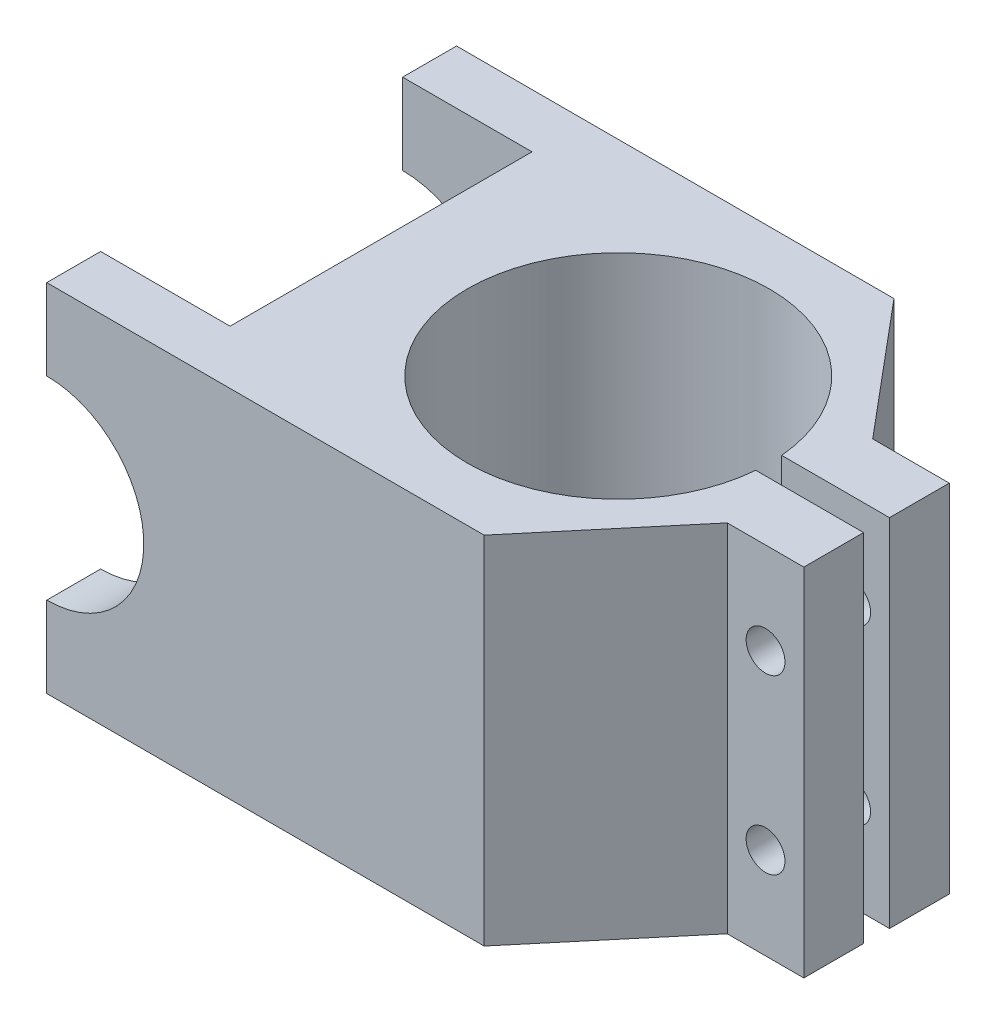
SolidWorks part; units mm, degrees
ref_plane "Front Plane" through (0, 0, 0) normal (0, 0, 1) x (1, 0, 0)
ref_plane "Top Plane" through (0, 0, 0) normal (0, 1, 0) x (1, 0, 0)
ref_plane "Right Plane" through (0, 0, 0) normal (1, 0, 0) x (0, 0, -1)
sketch "Sketch1" plane through (0, 0, 0) normal (0, 1, 0) x (1, 0, 0)
  line L0 (0, 0) -> (-66.726, 0) construction
  line L1 (-121.1334, 24.13) -> (-48.0271, 24.13)
  line L2 (-48.0271, 24.13) -> (-34.9656, 8.564)
  line L3 (-34.9656, 8.564) -> (-25.9488, 8.564)
  line L4 (-25.9488, 8.564) -> (-25.9488, 1.524)
  line L5 (-25.9488, 1.524) -> (-38.6488, 1.524)
  line L6 (-25.9488, -1.524) -> (-38.6488, -1.524)
  line L7 (-25.9488, -8.564) -> (-25.9488, -1.524)
  line L8 (-34.9656, -8.564) -> (-25.9488, -8.564)
  line L9 (-48.0271, -24.13) -> (-34.9656, -8.564)
  line L10 (-121.1334, -24.13) -> (-48.0271, -24.13)
  line L11 (-121.1334, 24.13) -> (-121.1334, 17.78)
  line L12 (-121.1334, 17.78) -> (-84.3034, 17.78)
  line L16 (-84.3034, 17.78) -> (-84.3034, -17.78)
  line L17 (-121.1334, -17.78) -> (-84.3034, -17.78)
  line L18 (-121.1334, -24.13) -> (-121.1334, -17.78)
  arc A0 (-38.6488, 1.524) -> (-38.6488, -1.524) centre (-56.3634, 0) ccw
  point P20 (-84.3034, 0)
  dimension "D3" = 1.524
  dimension "D8" = 17.78
  dimension "D11" = 27.94
  dimension "D1" = 24.13
  dimension "D2" = 12.7
  dimension "D4" = 20.32
  dimension "D5" = 50
  dimension "D6" = 9.0168
  dimension "D7" = 7.04
  dimension "D9" = 6.35
  dimension "D10" = 36.83
  dimension "D12" = 73.1063
  dimension "D13" = 95.1846
extrude "Boss-Extrude1" add sketch "Sketch1" along normal blind 41.91
ref_plane "Plane1" through (0, 0, 24.13) normal (0, 0, 1) x (1, 0, 0)
sketch "Sketch2" plane through (0, 0, 24.13) normal (0, 0, 1) x (1, 0, 0)
  line L0 (-121.1334, 20.955) -> (-99.5434, 20.955) construction
  line L1 (-121.1334, 41.91) -> (-121.1334, 0) construction
  circle A0 centre (-99.5434, 20.955) radius 11.43
  dimension "D1" = 21.59
extrude "Cut-Extrude1" cut sketch "Sketch2" against normal blind 56.388
sketch "Sketch3" plane through (0, 0, 24.13) normal (0, 0, 1) x (1, 0, 0)
  line L0 (-121.1334, 20.955) -> (-93.095, 20.955) construction
  line L25 (-121.1334, 41.91) -> (-121.1334, 0) construction
  line L26 (-121.1334, 22.479) -> (-100.0687, 22.479)
  line L27 (-100.0687, 22.479) -> (-100.0687, 19.431)
  line L28 (-100.0687, 19.431) -> (-121.1334, 19.431)
  line L29 (-121.1334, 19.431) -> (-121.1334, 22.479)
  line L30 (-121.1334, 22.479) -> (-121.1334, 27.305)
  line L31 (-121.1334, 27.305) -> (-114.7834, 27.305)
  line L32 (-114.7834, 27.305) -> (-104.401, 41.91)
  line L33 (-121.1334, 41.91) -> (-48.0271, 41.91) construction
  line L34 (-104.401, 41.91) -> (-121.1334, 41.91)
  line L35 (-121.1334, 41.91) -> (-121.1334, 27.305)
  line L36 (-121.1334, 0) -> (-121.1334, 14.605)
  line L37 (-104.401, 0) -> (-121.1334, 0)
  line L38 (-114.7834, 14.605) -> (-104.401, 0)
  line L39 (-121.1334, 14.605) -> (-114.7834, 14.605)
  dimension "D1" = 1.524
  dimension "D2" = 1.524
  dimension "D3" = 6.35
  dimension "D4" = 12.7
extrude "Cut-Extrude3" cut sketch "Sketch3" against normal blind 56.388 contours L39 L36 L37 L38 | L34 L35 L31 L32 | L0 L29 L28 L27 | L29 L0 L27 L26 region at (-110.601, 21.717, 24.13) region at (-110.601, 20.193, 24.13) region at (-114.9736, 35.7024, 24.13) region at (-114.9736, 6.2076, 24.13)
ref_plane "Plane2" through (0, 27.305, 0) normal (0, 1, 0) x (1, 0, 0)
sketch "Sketch4" plane through (0, 27.305, 0) normal (0, 1, 0) x (1, 0, 0)
  circle A0 centre (-117.9584, 20.955) radius 2.25
  circle A1 centre (-117.9584, -20.955) radius 2.25
  dimension "D1" = 4.5
extrude "Cut-Extrude4" cut sketch "Sketch4" against normal blind 56.388
ref_plane "Plane3" through (0, 0, 8.564) normal (0, 0, 1) x (1, 0, 0)
sketch "Sketch5" plane through (0, 0, 8.564) normal (0, 0, 1) x (1, 0, 0)
  line L0 (-25.9488, 20.955) -> (-31.4137, 20.955) construction
  line L1 (-25.9488, 41.91) -> (-25.9488, 0) construction
  circle A0 centre (-30.4572, 31.115) radius 2.286
  circle A1 centre (-30.4572, 10.795) radius 2.286
  dimension "D1" = 10.16
extrude "Cut-Extrude5" cut sketch "Sketch5" against normal blind 56.388
sketch "Sketch6" plane through (0, 0, -24.13) normal (0, 0, -1) x (-1, 0, 0)
  line L0 (99.5434, 0) -> (99.5434, 41.91)
  line L1 (48.0271, 0) -> (104.401, 0) construction
  line L2 (48.0271, 41.91) -> (104.401, 41.91) construction
  line L3 (99.5434, 41.91) -> (123.3879, 41.91)
  line L4 (123.3879, 41.91) -> (123.3879, -0.7874)
  line L5 (123.3879, -0.7874) -> (99.5434, 0)
  arc A0 (110.8713, 22.479) -> (110.8713, 19.431) centre (99.5434, 20.955) ccw construction
  arc A1 (110.8713, 22.479) -> (110.8713, 19.431) centre (99.5434, 20.955) ccw construction
extrude "Cut-Extrude6" cut sketch "Sketch6" against normal through all
hole_wizard "M4x0.7 Tapped Hole1" positions "Sketch9" profile "Sketch8" tap size "M4x0.7" standard "ANSI Metric"
sketch "Sketch9" plane through (-99.5434, 0, 0) normal (-1, 0, 0) x (0, 0, 1)
  line L0 (0, 41.91) -> (0, 0) construction
  line L1 (-17.78, 41.91) -> (17.78, 41.91) construction
  line L3 (-24.13, 20.955) -> (24.13, 20.955) construction
  line L4 (-24.13, 32.385) -> (-24.13, 9.525) construction
  line L5 (24.13, 9.525) -> (24.13, 32.385) construction
  line L7 (-17.78, 41.91) -> (-24.13, 41.91) construction
  line L8 (-20.955, 41.91) -> (-20.955, 38.1) construction
  point P0 (-20.955, 38.1)
  point P17 (-20.955, 3.81)
  point P18 (20.955, 3.81)
  point P19 (20.955, 38.1)
  dimension "D1" = 34.29
sketch "Sketch8" plane through (-99.5434, 38.1, -20.955) normal (0, 1, 0) x (0, 0, 1)
  line L0 (0, 0) -> (0, 12.4214)
  line L1 (0, 12.4214) -> (1.65, 11.43)
  line L2 (1.65, 11.43) -> (1.65, 0)
  line L5 (1.65, 0) -> (0, 0)
  line L10 (0, 12.4214) -> (-1.65, 11.43) construction
  line L11 (0, -6.35) -> (0, 107.95) construction
  dimension "Tap Drill Dia." = 3.3
  dimension "Tap Drill Depth" = 11.43
  dimension "Drill Angle" = 118
cosmetic thread "Hole Thread1"
cosmetic thread "Hole Thread2"
cosmetic thread "Hole Thread3"
cosmetic thread "Hole Thread4"
